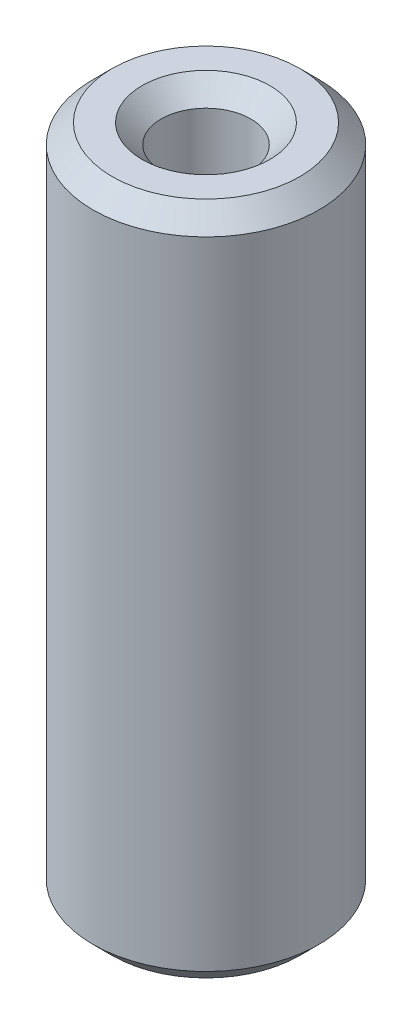
SolidWorks part; units mm, degrees
ref_plane "Front Plane" through (0, 0, 0) normal (0, 0, 1) x (1, 0, 0)
ref_plane "Top Plane" through (0, 0, 0) normal (0, 1, 0) x (1, 0, 0)
ref_plane "Right Plane" through (0, 0, 0) normal (1, 0, 0) x (0, 0, -1)
sketch "Sketch1" plane through (0, 0, 0) normal (0, 1, 0) x (1, 0, 0)
  circle A0 centre (0, 0) radius 20
  dimension "SLEEVE_OD" = 40
extrude "Boss-Extrude1" add sketch "Sketch1" along normal blind 119.4292
sketch "Sketch2" plane through (0, 0, 0) normal (0, 1, 0) x (1, 0, 0)
  circle A0 centre (0, 0) radius 7.9268
  dimension "BORE_D" = 15.8537
extrude "Cut-Extrude1" cut sketch "Sketch2" along normal through all
chamfer "Chamfer1" distance 3.3994 angle 45 4 edges at (0, 119.4292, 7.9268) (0, 0, 7.9268) (0, 0, 20) (0, 119.4292, 20)
